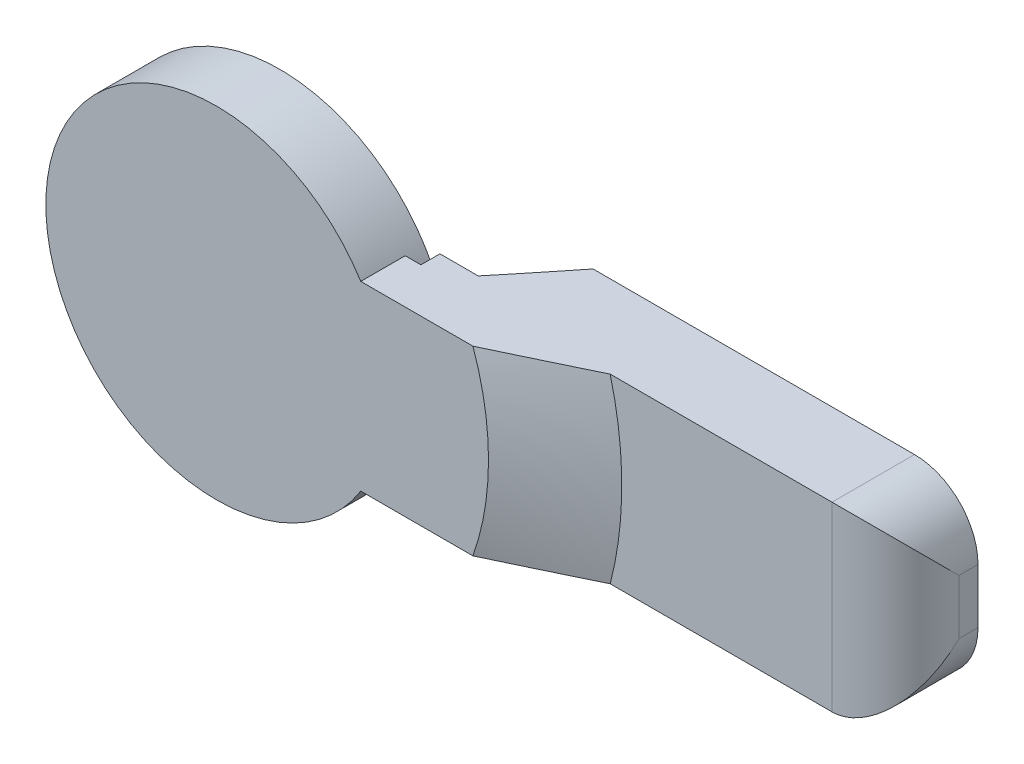
SolidWorks part; units mm, degrees
material "Custom Plastic"
ref_plane "Front Plane" through (0, 0, 0) normal (0, 0, 1) x (1, 0, 0)
ref_plane "Top Plane" through (0, 0, 0) normal (0, 1, 0) x (1, 0, 0)
ref_plane "Right Plane" through (0, 0, 0) normal (1, 0, 0) x (0, 0, -1)
sketch "Sketch1" plane through (0, 0, 0) normal (0, 0, 1) x (1, 0, 0)
  circle A0 centre (0, 0) radius 26.875
  dimension "D1" = 53.75
extrude "Boss-Extrude1" add sketch "Sketch1" along normal blind 2
sketch "Sketch2" plane through (0, 0, 2) normal (0, 0, 1) x (1, 0, 0)
  circle A0 centre (0, 0) radius 26.875
  circle A1 centre (0, 0) radius 25.125
  dimension "D1" = 50.25
  dimension "D2" = 53.75
extrude "Boss-Extrude2" add sketch "Sketch2" along normal blind 8
ref_plane "Plane1" through (0, 0, 20) normal (0, 0, 1) x (1, 0, 0)
sketch "Sketch3" plane through (0, 0, 20) normal (0, 0, 1) x (1, 0, 0)
  line L0 (100, 14.31) -> (22.7484, 14.31)
  line L5 (100, -14.31) -> (22.7484, -14.31)
  line L6 (100, 14.31) -> (100, -14.31)
  circle A3 centre (0, 0) radius 26.875 construction
  arc A4 (22.7484, 14.31) -> (22.7484, -14.31) centre (0, 0) cw
  dimension "D1" = 100
extrude "Boss-Extrude3" add sketch "Sketch3" against normal blind 13 contours L6 L0 A4 L5
chamfer "Chamfer1" distance 20 distance2 15 1 edges at (26.875, 0, 20) first distance on face at (24.8117, 0, 15)
chamfer "Chamfer2" distance 30 distance2 15 1 edges at (26.875, 0, 7) first distance on face at (62.4059, 0, 7)
sketch "Sketch8" plane through (0, 0, 10) normal (0, 0, 1) x (1, 0, 0)
  circle A0 centre (0, 0) radius 25.125
  circle A1 centre (0, 0) radius 26.875
  circle A2 centre (0, 0) radius 29
  line M4 (22.7484, -14.31) -> (31.2548, -14.31)
  line M6 (31.2548, 14.31) -> (22.7484, 14.31)
  dimension "D1" = 53.75
  dimension "D2" = 50.25
  dimension "D3" = 58
extrude "Cut-Extrude4" cut sketch "Sketch8" against normal blind 3 contours A2 A1 M4 M6 region at (26.1042, 7.5277, 10)
sketch "Sketch10" plane through (0, 0, 2) normal (0, 0, 1) x (1, 0, 0)
  line L0 (-2.5981, -1.5) -> (2.5981, -1.5)
  line L1 (-2.5981, 1.5) -> (2.5981, 1.5)
  line L2 (0, 1.5) -> (0, -1.5) construction
  circle A0 centre (0, 0) radius 5
  arc A1 (-2.5981, 1.5) -> (-2.5981, -1.5) centre (0, 0) ccw
  arc A2 (2.5981, -1.5) -> (2.5981, 1.5) centre (0, 0) ccw
  dimension "D1" = 10
  dimension "D2" = 6
  dimension "D3" = 3
extrude "Boss-Extrude4" add sketch "Sketch10" along normal blind 6
mirror "Mirror2" about plane through (0, 0, 20) normal (0, 0, -1) of bodies 110
delete or keep bodies "Body-Delete/Keep 1" type delete bodies bodies 110
fillet "Fillet1" radius 10 3 edges at (100, 0, 33) (100, -14.31, 26.5) (100, 14.31, 26.5)
